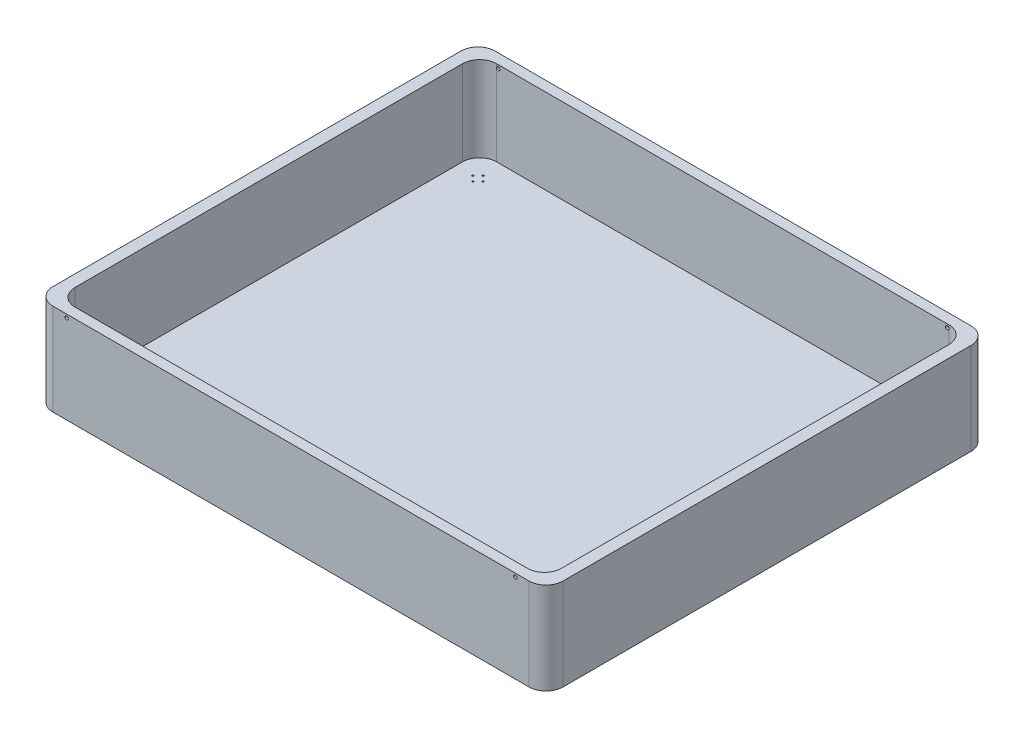
SolidWorks part; units mm, degrees
ref_plane "Спереди" through (0, 0, 0) normal (0, 0, 1) x (1, 0, 0)
ref_plane "Сверху" through (0, 0, 0) normal (0, 1, 0) x (1, 0, 0)
ref_plane "Справа" through (0, 0, 0) normal (1, 0, 0) x (0, 0, -1)
sketch "Эскиз1" plane through (0, 0, 0) normal (0, 1, 0) x (1, 0, 0)
  line L1 (-700, -650) -> (700, -650)
  line L2 (-750, -600) -> (-750, 600)
  line L3 (-700, 650) -> (700, 650)
  line L4 (750, -600) -> (750, 600)
  line L5 (-750, -650) -> (750, 650) construction
  line L6 (-750, 650) -> (750, -650) construction
  arc A0 (-700, -650) -> (-750, -600) centre (-700, -600) cw
  arc A1 (700, -650) -> (750, -600) centre (700, -600) ccw
  arc A2 (700, 650) -> (750, 600) centre (700, 600) cw
  arc A3 (-750, 600) -> (-700, 650) centre (-700, 600) cw
  point P0 (0, 0)
  dimension "D3" = 50
  dimension "D1" = 1300
  dimension "D2" = 1500
extrude "Бобышка-Вытянуть1" add sketch "Эскиз1" along normal blind 20 contours L3 A2 L4 A1 L1 A0 L2 A3
sketch "Эскиз2" plane through (0, 20, 0) normal (0, 1, 0) x (1, 0, 0)
  line L1 (700, -650) -> (-700, -650)
  line L2 (750, -600) -> (750, 600)
  line L3 (700, 650) -> (-700, 650)
  line L4 (-750, -600) -> (-750, 600)
  line L5 (750, -650) -> (-750, 650) construction
  line L6 (750, 650) -> (-750, -650) construction
  line L7 (665.3846, -620) -> (-665.3846, -620)
  line L8 (715.3846, -570) -> (715.3846, 570)
  line L9 (665.3846, 620) -> (-665.3846, 620)
  line L10 (-715.3846, -570) -> (-715.3846, 570)
  line L11 (715.3846, -620) -> (-715.3846, 620) construction
  line L12 (715.3846, 620) -> (-715.3846, -620) construction
  arc A0 (750, 600) -> (700, 650) centre (700, 600) ccw
  arc A1 (700, -650) -> (750, -600) centre (700, -600) ccw
  arc A2 (-700, 650) -> (-750, 600) centre (-700, 600) ccw
  arc A3 (-700, -650) -> (-750, -600) centre (-700, -600) cw
  arc A4 (715.3846, 570) -> (665.3846, 620) centre (665.3846, 570) ccw
  arc A5 (665.3846, -620) -> (715.3846, -570) centre (665.3846, -570) ccw
  arc A6 (-665.3846, -620) -> (-715.3846, -570) centre (-665.3846, -570) cw
  arc A7 (-665.3846, 620) -> (-715.3846, 570) centre (-665.3846, 570) ccw
  point P0 (0, 0)
  point P18 (0, 0)
  dimension "D3" = 50
  dimension "D5" = 50
  dimension "D1" = 1500
  dimension "D2" = 1300
  dimension "D4" = 30
extrude "Бобышка-Вытянуть2" add sketch "Эскиз2" along normal blind 250
sketch "Эскиз3" plane through (0, 0, 0) normal (0, -1, 0) x (1, 0, 0)
  line L0 (-750, 600) -> (-750, -600) construction
  line L1 (-650, -550) -> (650, -550)
  line L2 (-650, -550) -> (-650, 550)
  line L3 (-650, 550) -> (650, 550)
  line L4 (650, -550) -> (650, 550)
  line L5 (-650, -550) -> (650, 550) construction
  line L6 (-650, 550) -> (650, -550) construction
  line L7 (-700, 650) -> (700, 650) construction
  line L8 (0, 0) -> (650, 0) construction
  line L9 (0, 0) -> (0, 550) construction
  circle A0 centre (-650, 550) radius 15
  circle A1 centre (-650, 535) radius 2.5
  circle A2 centre (-665, 550) radius 2.5
  circle A3 centre (-650, 565) radius 2.5
  circle A4 centre (-635, 550) radius 2.5
  circle A5 centre (650, 535) radius 2.5
  circle A6 centre (635, 550) radius 2.5
  circle A7 centre (665, 550) radius 2.5
  circle A8 centre (650, 565) radius 2.5
  circle A9 centre (650, -565) radius 2.5
  circle A10 centre (635, -550) radius 2.5
  circle A11 centre (650, -535) radius 2.5
  circle A12 centre (665, -550) radius 2.5
  circle A13 centre (-635, -550) radius 2.5
  circle A14 centre (-650, -535) radius 2.5
  circle A15 centre (-665, -550) radius 2.5
  circle A16 centre (-650, -565) radius 2.5
  point P1 (0, 0)
  point P22 (-650, 550)
  dimension "D3" = 30
  dimension "D4" = 5
  dimension "D7" = 30
  dimension "D1" = 100
  dimension "D2" = 100
  dimension "D6" = 15
  dimension "D5" = 4
extrude "Вырез-Вытянуть1" cut sketch "Эскиз3" against normal blind 250 contours A16 | A3 | A2 | A4 | A1 | A7 | A8 | A6 | A5 | A11 | A10 | A12 | A9 | A14 | A15 | A13 region at (-650, 0, -565)
sketch "Эскиз4" plane through (0, 0, -650) normal (0, 0, -1) x (-1, 0, 0)
  line L0 (700, 0) -> (-700, 0) construction
  line L1 (750, 270) -> (750, 0) construction
  circle A0 centre (660, 260) radius 5
  dimension "D1" = 10
  dimension "D2" = 260
  dimension "D3" = 90
extrude "Вырез-Вытянуть2" cut sketch "Эскиз4" against normal blind 1500
ref_plane "Плоскость1" through (0, 0, 0) normal (-1, 0, 0) x (0, 0, 1)
mirror "Зеркальное отражение1" about plane through (0, 0, 0) normal (-1, 0, 0) of "Вырез-Вытянуть2"
